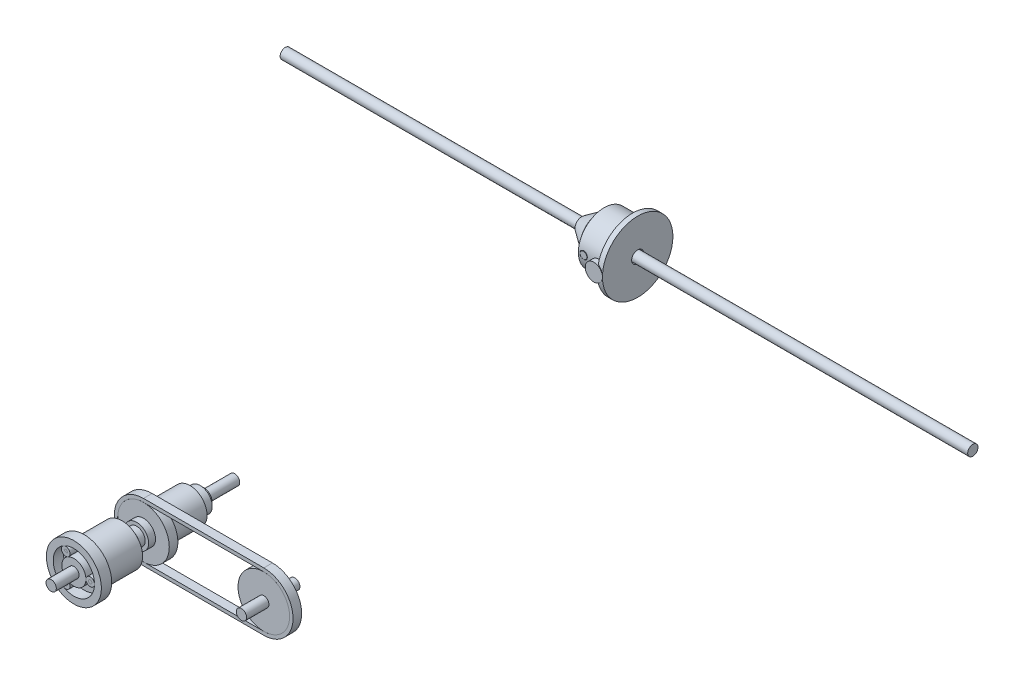
SolidWorks part; units mm, degrees
other "RD S Gear Inner"
other "RD S Gear Outer"
other "RD L Gear Left"
other "RD L Gear Right"
other "RD Ring Gear"
other "RD Pinion"
other "RD S Gear Inner"
ref_plane "Front Plane" through (0, 0, 0) normal (0, 0, 1) x (1, 0, 0)
ref_plane "Top Plane" through (0, 0, 0) normal (0, 1, 0) x (1, 0, 0)
ref_plane "Right Plane" through (0, 0, 0) normal (1, 0, 0) x (0, 0, -1)
sketch "Top View Layout" plane through (0, 0, 0) normal (0, 1, 0) x (1, 0, 0)
  line L0 (-100, 125) -> (100, 125)
  line L1 (0, 125) -> (0, -125)
  line L2 (-100, -125) -> (100, -125)
  line L3 (0, -15) -> (35, -15) construction
  line L4 (35, -15) -> (35, -125) construction
  line L5 (2.5, 114.75) -> (2.5, 135.25) construction
  line L6 (-2.5, 114.75) -> (2.5, 114.75) construction
  line L7 (-8.75, 127) -> (-2.75, 127) construction
  line L8 (-2.5, 114.75) -> (2.5, 114.75) construction
  line L9 (-2.5, 114.75) -> (-2.5, 116.25) construction
  line L10 (-2.5, 116.25) -> (2.5, 116.25) construction
  line L11 (2.5, 114.75) -> (2.5, 116.25) construction
  line L12 (2.5, 135.25) -> (1, 135.25) construction
  line L13 (2.5, 135.25) -> (2.5, 114.75) construction
  line L14 (2.5, 114.75) -> (1, 114.75) construction
  line L15 (1, 135.25) -> (1, 114.75) construction
  line L16 (-4.25, 128.5) -> (-2.75, 128.5) construction
  line L17 (-4.25, 128.5) -> (-4.25, 121.5) construction
  line L18 (-4.25, 121.5) -> (-2.75, 121.5) construction
  line L19 (-2.75, 128.5) -> (-2.75, 121.5) construction
  line L20 (-4.25, 128.5) -> (-2.75, 121.5) construction
  line L21 (-4.25, 121.5) -> (-2.75, 128.5) construction
  line L22 (-8.75, 128.5) -> (-7.25, 128.5) construction
  line L23 (-8.75, 128.5) -> (-8.75, 121.5) construction
  line L24 (-8.75, 121.5) -> (-7.25, 121.5) construction
  line L25 (-7.25, 128.5) -> (-7.25, 121.5) construction
  line L26 (-8.75, 128.5) -> (-7.25, 121.5) construction
  line L27 (-8.75, 121.5) -> (-7.25, 128.5) construction
  line L28 (-8.75, 123) -> (-2.75, 123) construction
  line L29 (-5.75, 123) -> (-5.75, 120.2863) construction
  line L30 (-5.75, 127) -> (-5.75, 129.2691) construction
  point P8 (0, 114.75)
  point P9 (0, 0)
  point P11 (2.5, 125)
  point P16 (2.5, 125)
  point P19 (0, 114.75)
  point P23 (-3.5, 125)
  point P28 (-8, 125)
  dimension "D1" = 250
  dimension "D2" = 200
  dimension "D3" = 35
  dimension "D4" = 15
  dimension "D5" = 5
  dimension "D6" = 20.5
  dimension "D7" = 1.5
  dimension "D8" = 1.5
  dimension "D9" = 1.5
  dimension "D10" = 7
  dimension "D11" = 3.5
  dimension "D12" = 8
  dimension "D13" = 1.5
  dimension "D14" = 1.5
ref_plane "Left" through (100, 0, 0) normal (-1, 0, 0) x (0, 0, 1)
ref_plane "Right" through (-100, 0, 0) normal (-1, 0, 0) x (0, 0, 1)
sketch "Left Wheels" plane through (100, 0, 0) normal (-1, 0, 0) x (0, 0, 1)
  circle A0 centre (125, 0) radius 25
  circle A1 centre (-125, 0) radius 25
  dimension "D1" = 50
  dimension "D2" = 50
sketch "Right Wheels" plane through (-100, 0, 0) normal (-1, 0, 0) x (0, 0, 1)
  circle A0 centre (-125, 0) radius 25 construction
  circle A1 centre (125, 0) radius 25 construction
  circle A2 centre (-125, 0) radius 25
  circle A3 centre (125, 0) radius 25
ref_plane "Rear Differential Pinion Plane" through (0, 0, -114.75) normal (0, 0, 1) x (1, 0, 0)
sketch "Rear Differential Pinion Profile" plane through (0, 0, -114.75) normal (0, 0, 1) x (1, 0, 0)
  circle A0 centre (0, 0) radius 2.5
ref_plane "Rear Differential Ring Gear Plane" through (2.5, 0, 0) normal (1, 0, 0) x (0, 0, -1)
ref_plane "Rear Axle" through (0, 0, -125) normal (0, 0, 1) x (1, 0, 0)
sketch "Rear Differential Ring Gear Profile" plane through (2.5, 0, 0) normal (1, 0, 0) x (0, 0, -1)
  line L0 (114.75, 0) -> (135.25, 0) construction
  circle A0 centre (125, 0) radius 10.25
extrude "Rear Differential Pinion" add sketch "Rear Differential Pinion Profile" against normal blind 1.5 contours A0
extrude "Rear Differential Ring Gear" add sketch "Rear Differential Ring Gear Profile" against normal blind 1.5 separate body contours A0
ref_plane "RD Inner L Gear Plane" through (-2.75, 0, 0) normal (1, 0, 0) x (0, 0, -1)
ref_plane "RD Outer L Gear Plane" through (-8.75, 0, 0) normal (1, 0, 0) x (0, 0, -1)
sketch "RD Inner L Gear Profile" plane through (-2.75, 0, 0) normal (1, 0, 0) x (0, 0, -1)
  circle A0 centre (125, 0) radius 3.5
sketch "RD Outer L Gear Profile" plane through (-8.75, 0, 0) normal (1, 0, 0) x (0, 0, -1)
  line L0 (128.5, 0) -> (121.5, 0) construction
  circle A0 centre (125, 0) radius 3.5
ref_plane "RD Inner S Gear Plane" through (0, 0, -121.5) normal (0, 0, 1) x (1, 0, 0)
ref_plane "RD Outer S Gear Plane" through (0, 0, -128.5) normal (0, 0, 1) x (1, 0, 0)
sketch "RD Inner S Gear Profile" plane through (0, 0, -121.5) normal (0, 0, 1) x (1, 0, 0)
  line L0 (-8.75, 0) -> (-7.25, 0) construction
  circle A0 centre (-5.75, 0) radius 3
sketch "RD Outer S Gear Profile" plane through (0, 0, -128.5) normal (0, 0, 1) x (1, 0, 0)
  line L0 (-8.75, 0) -> (-7.25, 0) construction
  circle A2 centre (-5.75, 0) radius 3
extrude "RD Outer L Gear Extrude" add sketch "RD Outer L Gear Profile" along normal blind 1.5 separate body contours A0
extrude "RD Inner L Gear Extrude" add sketch "RD Inner L Gear Profile" against normal blind 1.5 separate body contours A0
extrude "RD Outer S Gear Extrude" add sketch "RD Outer S Gear Profile" along normal blind 1.5 separate body contours A2
extrude "RD Inner S Gear Extrude" add sketch "RD Inner S Gear Profile" against normal blind 1.5 separate body contours A0
sketch "RD Ring Gear Case Profile" plane through (1, 0, 0) normal (-1, 0, 0) x (0, 0, 1)
  line L0 (-121.5, 3.2113) -> (-121.5, -3.2113)
  line L1 (-128.5, 3.2113) -> (-128.5, -3.2113)
  line L2 (-121.5, 6.6332) -> (-121.5, 3.2113) construction
  line L3 (-128.5, 6.6332) -> (-128.5, 3.2113) construction
  line L4 (-121.5, -3.2113) -> (-121.5, -6.6332) construction
  line L5 (-128.5, -3.2113) -> (-128.5, -6.6332) construction
  circle A0 centre (-125, 0) radius 7.5
  arc A1 (-121.5, 3.2113) -> (-128.5, 3.2113) centre (-125, 0) ccw
  arc A2 (-121.5, -3.2113) -> (-121.5, 3.2113) centre (-125, 0) ccw construction
  arc A3 (-128.5, 3.2113) -> (-128.5, -3.2113) centre (-125, 0) ccw construction
  arc A4 (-128.5, -3.2113) -> (-121.5, -3.2113) centre (-125, 0) ccw
  point P7 (-121.5, 0)
  dimension "D1" = 15
  dimension "D2" = 9.5
extrude "RD Ring Gear Case " add sketch "RD Ring Gear Case Profile" along normal blind 8.25
sketch "Sketch11" plane through (-7.25, 0, 0) normal (-1, 0, 0) x (0, 0, 1)
  circle A0 centre (-125, 0) radius 5.5
  circle A1 centre (-125, 0) radius 4.75
  arc A2 (-121.5, 3.2113) -> (-128.5, 3.2113) centre (-125, 0) ccw construction
  dimension "D1" = 11
extrude "Boss-Extrude8" add sketch "Sketch11" along normal up to vertex up to point (-8.75, 0, -128.5)
fillet "Fillet1" radius 2 1 edges at (-7.25, 0, -119.5)
sketch "Sketch12" plane through (0, 0, -125) normal (0, 0, 1) x (1, 0, 0)
  line L0 (-8.75, 0) -> (-13.75, 0) construction
  line L1 (-8.75, 0) -> (-7.25, 0) construction
  line L2 (-8.75, 0) -> (-7.25, 0) construction
  line L3 (-100, 0) -> (100, 0) construction
  line L4 (-100, 0) -> (100, 0) construction
  line L5 (-8.75, 5.5) -> (-8.75, -5.5) construction
  line L6 (-13.75, 0) -> (-13.75, 2)
  line L7 (-13.75, 2) -> (-8.75, 5.5)
  line L8 (-13.75, 0) -> (-8.75, 0)
  line L9 (-8.75, 0) -> (-8.75, 5.5)
  point P15 (-13.75, 1)
  dimension "D1" = 5
  dimension "D2" = 2
revolve "Revolve1" add sketch "Sketch12" angle 360 about L0
sketch "Sketch13" plane through (2.5, 0, 0) normal (1, 0, 0) x (0, 0, -1)
  circle A0 centre (125, 0) radius 1.75
  dimension "D1" = 3.5
extrude "Cut-Extrude1" cut sketch "Sketch13" against normal through all
sketch "Sketch14" plane through (0, 0, -121.5) normal (0, 0, 1) x (1, 0, 0)
  circle A0 centre (-5.75, 0) radius 1
  dimension "D1" = 2
extrude "Boss-Extrude9" add sketch "Sketch14" along normal blind 4
sketch "Sketch15" plane through (0, 0, -121.5) normal (0, 0, 1) x (1, 0, 0)
  circle A0 centre (-5.75, 0) radius 1.1
  dimension "D1" = 2.2
extrude "Cut-Extrude2" cut sketch "Sketch15" against normal through all both and the other way through all
extrude "Boss-Extrude10" add sketch "Sketch14<2>" against normal blind 4 from surface starting at face at (-2.75, 0, -128.5)
sketch "Sketch14<2>" plane through (0, 0, -121.5) normal (0, 0, 1) x (1, 0, 0) same geometry as "Sketch14"
sketch "Sketch16" plane through (-8.75, 0, 0) normal (-1, 0, 0) x (0, 0, 1)
  circle A0 centre (-125, 0) radius 1.5
  dimension "D1" = 3
extrude "Boss-Extrude11" add sketch "Sketch16" along normal up to vertex (91.25 mm away) up to point (-100, 0, -125)
sketch "Sketch17" plane through (-2.75, 0, 0) normal (1, 0, 0) x (0, 0, -1)
  circle A0 centre (125, 0) radius 1.5 construction
  circle A1 centre (125, 0) radius 1.5
extrude "Boss-Extrude12" add sketch "Sketch17" along normal up to vertex (102.75 mm away) up to point (100, 0, -125)
sketch "Transfer Case Layout" plane through (0, 0, 0) normal (0, 1, 0) x (1, 0, 0)
  line L0 (0, 125) -> (0, -125) construction
  line L1 (-7.5, -13.75) -> (7.5, -13.75)
  line L2 (-7.5, -13.75) -> (-7.5, -16.25)
  line L3 (-7.5, -16.25) -> (7.5, -16.25)
  line L4 (7.5, -13.75) -> (7.5, -16.25)
  line L5 (-7.5, -13.75) -> (7.5, -16.25) construction
  line L6 (-7.5, -16.25) -> (7.5, -13.75) construction
  line L7 (27.5, -13.75) -> (42.5, -13.75)
  line L8 (27.5, -13.75) -> (27.5, -16.25)
  line L9 (27.5, -16.25) -> (42.5, -16.25)
  line L10 (42.5, -13.75) -> (42.5, -16.25)
  line L11 (27.5, -13.75) -> (42.5, -16.25) construction
  line L12 (27.5, -16.25) -> (42.5, -13.75) construction
  line L13 (2.5, -17.25) -> (-2.5, -17.25)
  line L14 (2.5, -17.25) -> (2.5, -16.25)
  line L15 (2.5, -16.25) -> (-2.5, -16.25)
  line L16 (-2.5, -17.25) -> (-2.5, -16.25)
  line L17 (2.5, -17.25) -> (-2.5, -16.25) construction
  line L18 (2.5, -16.25) -> (-2.5, -17.25) construction
  line L19 (-2, -4.75) -> (-2, -10.75)
  line L20 (3.5, -18.25) -> (-3.5, -18.25)
  line L21 (3.5, -18.25) -> (3.5, -16.25)
  line L22 (3.5, -16.25) -> (-3.5, -16.25)
  line L23 (-3.5, -18.25) -> (-3.5, -16.25)
  line L24 (3.5, -18.25) -> (-3.5, -16.25) construction
  line L25 (3.5, -16.25) -> (-3.5, -18.25) construction
  line L26 (2.5, -20) -> (-2.5, -20)
  line L27 (2.5, -20) -> (2.5, -17.5)
  line L28 (2.5, -17.5) -> (-2.5, -17.5)
  line L29 (-2.5, -20) -> (-2.5, -17.5)
  line L30 (2.5, -20) -> (-2.5, -17.5) construction
  line L31 (2.5, -17.5) -> (-2.5, -20) construction
  line L32 (-3.5, -9.25) -> (3.5, -9.25)
  line L33 (-3.5, -9.25) -> (-3.5, -10.75)
  line L34 (-3.5, -10.75) -> (3.5, -10.75)
  line L35 (3.5, -9.25) -> (3.5, -10.75)
  line L36 (-3.5, -9.25) -> (3.5, -10.75) construction
  line L37 (-3.5, -10.75) -> (3.5, -9.25) construction
  line L38 (-3.5, -4.75) -> (3.5, -4.75)
  line L39 (-3.5, -4.75) -> (-3.5, -6.25)
  line L40 (-3.5, -6.25) -> (3.5, -6.25)
  line L41 (3.5, -4.75) -> (3.5, -6.25)
  line L42 (-3.5, -4.75) -> (3.5, -6.25) construction
  line L43 (-3.5, -6.25) -> (3.5, -4.75) construction
  line L44 (2, -4.75) -> (2, -10.75)
  line L45 (0, -6.25) -> (0, -9.25) construction
  line L46 (-5, -2.75) -> (5, -2.75) construction
  line L47 (-5, -2.75) -> (-5, -12.75) construction
  line L48 (-5, -12.75) -> (5, -12.75) construction
  line L49 (5, -2.75) -> (5, -12.75) construction
  line L50 (-5, -2.75) -> (5, -12.75) construction
  line L51 (-5, -12.75) -> (5, -2.75) construction
  line L52 (-6, -22.5) -> (-6, -24)
  line L53 (-2.5, -1.75) -> (2.5, -1.75)
  line L54 (-2.5, -1.75) -> (-2.5, -2.75)
  line L55 (-2.5, -2.75) -> (2.5, -2.75)
  line L56 (2.5, -1.75) -> (2.5, -2.75)
  line L57 (-2.5, -1.75) -> (2.5, -2.75) construction
  line L58 (-2.5, -2.75) -> (2.5, -1.75) construction
  line L59 (-2.5, 1.25) -> (2.5, 1.25)
  line L60 (-2.5, 1.25) -> (-2.5, -0.75)
  line L61 (-2.5, -0.75) -> (2.5, -0.75)
  line L62 (2.5, 1.25) -> (2.5, -0.75)
  line L63 (-2.5, 1.25) -> (2.5, -0.75) construction
  line L64 (-2.5, -0.75) -> (2.5, 1.25) construction
  line L65 (3.5, 0.25) -> (-3.5, 0.25)
  line L66 (3.5, 0.25) -> (3.5, -2.25)
  line L67 (3.5, -2.25) -> (-3.5, -2.25)
  line L68 (-3.5, 0.25) -> (-3.5, -2.25)
  line L69 (3.5, 0.25) -> (-3.5, -2.25) construction
  line L70 (3.5, -2.25) -> (-3.5, 0.25) construction
  line L71 (-2.5, -22.5) -> (2.5, -22.5)
  line L72 (-2.5, -22.5) -> (-2.5, -27.5)
  line L73 (-2.5, -27.5) -> (2.5, -27.5)
  line L74 (2.5, -22.5) -> (2.5, -27.5)
  line L75 (-2.5, -22.5) -> (2.5, -27.5) construction
  line L76 (-2.5, -27.5) -> (2.5, -22.5) construction
  line L77 (-6, -24) -> (6, -24)
  line L78 (6, -24) -> (6, -22.5)
  line L79 (6, -22.5) -> (-6, -22.5)
  line L80 (-4.5, -22.5) -> (-4.5, -24)
  line L81 (4.5, -22.5) -> (4.5, -24)
  line L82 (-6, -24) -> (-6, -33.5) construction
  line L83 (2.5, -29.5) -> (-2.5, -29.5)
  line L84 (2.5, -29.5) -> (2.5, -28)
  line L85 (2.5, -28) -> (-2.5, -28)
  line L86 (-2.5, -29.5) -> (-2.5, -28)
  line L87 (2.5, -29.5) -> (-2.5, -28) construction
  line L88 (2.5, -28) -> (-2.5, -29.5) construction
  line L89 (-4.5, -26.5) -> (4.5, -26.5)
  line L90 (-4.5, -26.5) -> (-4.5, -29.5)
  line L91 (-4.5, -29.5) -> (4.5, -29.5)
  line L92 (4.5, -26.5) -> (4.5, -29.5)
  line L93 (-4.5, -26.5) -> (4.5, -29.5) construction
  line L94 (-4.5, -29.5) -> (4.5, -26.5) construction
  line L95 (6, -24) -> (6, -33.5) construction
  line L96 (-3.5, -33.5) -> (-3.5, -36.5)
  line L97 (6, -36.5) -> (-6, -36.5)
  line L98 (6, -36.5) -> (6, -33.5)
  line L99 (6, -33.5) -> (-6, -33.5)
  line L100 (-6, -36.5) -> (-6, -33.5)
  line L101 (6, -36.5) -> (-6, -33.5) construction
  line L102 (6, -33.5) -> (-6, -36.5) construction
  line L103 (3.5, -33.5) -> (3.5, -36.5)
  line L104 (0, -28) -> (0, -43.1129)
  line L109 (8, -36.5) -> (-8, -36.5)
  line L110 (8, -36.5) -> (8, -33.5)
  line L111 (8, -33.5) -> (-8, -33.5)
  line L112 (-8, -36.5) -> (-8, -33.5)
  line L113 (8, -36.5) -> (-8, -33.5) construction
  line L114 (8, -33.5) -> (-8, -36.5) construction
  line L115 (0, -27.5) -> (0, -9.25)
  line L116 (0, -6.25) -> (0, -1.75)
  line L117 (0, -0.75) -> (0, 11.0375)
  line L118 (35, -22.7597) -> (35, -7.2403)
  point P0 (0, -15)
  point P6 (35, -15)
  point P12 (0, -16.75)
  point P19 (0, -17.25)
  point P24 (0, -18.75)
  point P29 (0, -10)
  point P34 (0, -5.5)
  point P43 (0, -7.75)
  point P50 (0, -2.25)
  point P55 (0, 0.25)
  point P60 (0, -1)
  point P65 (0, -25)
  point P72 (0, -22.5)
  point P79 (0, -28.75)
  point P84 (0, -28)
  point P92 (0, -35)
  point P98 (0, -35)
  point P99 (0, -35)
  point P110 (0, 0)
  point P113 (35, -15)
  point P114 (0, 0)
  point P115 (0, 0)
  point P116 (0, 0)
  point P117 (0, 0)
  point P118 (0, 0)
  point P119 (0, 0)
  point P120 (0, 0)
  point P121 (0, 0)
  point P122 (0, 0)
  point P123 (0, 0)
  point P124 (0, 0)
  point P125 (0, 0)
  point P126 (6, -33.5)
  point P127 (0, 0)
  point P128 (0, 0)
  point P129 (0, 0)
  point P130 (0, 0)
  point P131 (0, 0)
  point P132 (0, 0)
  point P133 (2.5, -1.75)
  point P134 (0, 0)
  point P135 (0, 0)
  point P136 (0, 0)
  point P137 (0, 0)
  point P138 (0, 0)
  point P139 (0, 0)
  point P140 (0, 0)
  point P141 (0, 0)
  point P142 (0, 0)
  point P143 (0, 0)
  point P144 (0, 0)
  point P145 (0, 0)
  point P146 (0, 0)
  point P147 (0, 0)
  point P148 (0, 0)
  point P149 (0, 0)
  dimension "D1" = 2.5
  dimension "D2" = 2.5
  dimension "D3" = 15
  dimension "D4" = 15
  dimension "D5" = 1
  dimension "D6" = 5
  dimension "D7" = 7
  dimension "D8" = 2
  dimension "D9" = 0.25
  dimension "D10" = 2.5
  dimension "D11" = 7
  dimension "D12" = 5
  dimension "D13" = 1.5
  dimension "D14" = 1.5
  dimension "D15" = 1.5
  dimension "D16" = 1.5
  dimension "D17" = 6
  dimension "D18" = 2
  dimension "D19" = 1.5
  dimension "D20" = 5
  dimension "D21" = 1
  dimension "D22" = 2
  dimension "D23" = 1
  dimension "D24" = 7
  dimension "D25" = 2.5
  dimension "D26" = 0.5
  dimension "D27" = 5
  dimension "D28" = 5
  dimension "D29" = 10
  dimension "D30" = 1.5
  dimension "D31" = 12
  dimension "D32" = 1.5
  dimension "D33" = 1.5
  dimension "D34" = 1.5
  dimension "D35" = 0.5
  dimension "D36" = 3
  dimension "D37" = 3
  dimension "D38" = 20
  dimension "D39" = 2.5
  dimension "D40" = 2.5
  dimension "D41" = 7
  dimension "D42" = 2
  dimension "D43" = 16
ref_plane "FWD Sprocket Plane" through (0, 0, 15) normal (0, 0, 1) x (1, 0, 0)
sketch "Sketch19" plane through (0, 0, 15) normal (0, 0, 1) x (1, 0, 0)
  circle A0 centre (35, 0) radius 7.5
  circle A1 centre (0, 0) radius 7.5
  point P6 (7.5, 0)
  point P9 (27.5, 0)
extrude "FWD Sprockets" add sketch "Sketch19" along normal up to vertex (1.25 mm away) and the other way up to vertex (1.25 mm away) separate body up to point (-7.5, 0, 16.25) other way up to point (-7.5, 0, 13.75)
sketch "Sketch20" plane through (0, 0, 15) normal (0, 0, 1) x (1, 0, 0)
  line L0 (0, 8.5) -> (35, 8.5)
  line L1 (0, -8.5) -> (35, -8.5)
  line L2 (0, 7.5) -> (35, 7.5)
  line L3 (0, -7.5) -> (35, -7.5)
  circle A0 centre (0, 0) radius 7.5 construction
  arc A1 (0, 7.5) -> (0, -7.5) centre (0, 0) ccw
  circle A2 centre (35, 0) radius 7.5 construction
  arc A3 (35, -7.5) -> (35, 7.5) centre (35, 0) ccw
  arc A4 (0, 8.5) -> (0, -8.5) centre (0, 0) ccw
  arc A5 (35, -8.5) -> (35, 8.5) centre (35, 0) ccw
  arc A6 (4, -7.5) -> (4, 7.5) centre (0, 0) ccw construction
  arc A7 (0, -7.5) -> (0, 7.5) centre (0, 0) ccw construction
  arc A8 (35, 7.5) -> (35, -7.5) centre (35, 0) ccw construction
  arc A9 (31, 7.5) -> (31, -7.5) centre (35, 0) ccw construction
  arc A10 (4, 7.5) -> (0, 8.5) centre (0, 0) ccw construction
  arc A11 (35, 8.5) -> (31, 7.5) centre (35, 0) ccw construction
  arc A12 (31, -7.5) -> (35, -8.5) centre (35, 0) ccw construction
  arc A13 (0, -8.5) -> (4, -7.5) centre (0, 0) ccw construction
  dimension "D1" = 1
  dimension "D2" = 1
extrude "FWD Sprocket Chain" add sketch "Sketch20" along normal up to surface and the other way up to surface separate body up to face at (7.5, 0, 16.25) other way up to face at (7.5, 0, 13.75)
sketch "Sketch21" plane through (0, 0, 16.25) normal (0, 0, 1) x (1, 0, 0)
  circle A0 centre (0, 0) radius 2.5
  point P3 (2.5, 0)
extrude "FWD Sprocket Dog Gear" add sketch "Sketch21" along normal up to vertex (1 mm away) up to point (-2.5, 0, 17.25)
ref_plane "Mode Sleeve Gear Plane" through (0, 0, 18.25) normal (0, 0, 1) x (1, 0, 0)
sketch "Sketch22" plane through (0, 0, 18.25) normal (0, 0, 1) x (1, 0, 0)
  circle A0 centre (0, 0) radius 3.5
  circle A1 centre (0, 0) radius 2.5 construction
  circle A2 centre (0, 0) radius 2.5
extrude "Mode Sleeve Gear" add sketch "Sketch22" against normal up to vertex (2 mm away) separate body up to point (3.5, 0, 16.25)
sketch "Sketch23" plane through (0, 0, 18.25) normal (0, 0, 1) x (1, 0, 0)
  circle A0 centre (0, 0) radius 2.5 construction
  circle A1 centre (0, 0) radius 2.5
extrude "Mode Sleeve Main Shaft Gear" add sketch "Sketch23" along normal up to vertex (1.75 mm away) separate body up to point (2.5, 0, 20)
ref_plane "Range Sleeve Rear Plane" through (0, 0, 22.5) normal (0, 0, 1) x (1, 0, 0)
sketch "Sketch24" plane through (0, 0, 22.5) normal (0, 0, 1) x (1, 0, 0)
  circle A0 centre (0, 0) radius 2.5
extrude "Main Shaft Range Sleeve Gear" add sketch "Sketch24" along normal up to vertex (5 mm away) separate body up to point (-2.5, 0, 27.5)
sketch "Sketch25" plane through (0, 0, 22.5) normal (0, 0, 1) x (1, 0, 0)
  circle A0 centre (0, 0) radius 6
  circle A3 centre (0, 0) radius 4.5
extrude "Carrier Range Sleeve Gear" add sketch "Sketch25" along normal up to vertex (1.5 mm away) separate body up to point (6, 0, 24)
ref_plane "Range Sleeve Input Shaft Side" through (0, 0, 29.5) normal (0, 0, 1) x (1, 0, 0)
sketch "Sketch27" plane through (0, 0, 29.5) normal (0, 0, 1) x (1, 0, 0)
  circle A0 centre (0, 0) radius 2.5
extrude "Input Range Sleeve Gear" add sketch "Sketch27" against normal up to vertex (1.5 mm away) separate body up to point (2.5, 0, 28)
sketch "Sketch28" plane through (0, 0, 29.5) normal (0, 0, 1) x (1, 0, 0)
  circle A0 centre (0, 0) radius 4.5
  circle A1 centre (0, 0) radius 2.5 construction
  circle A2 centre (0, 0) radius 2.5
extrude "Range Sleeve Sleeve Gear" add sketch "Sketch28" against normal up to vertex (3 mm away) separate body up to point (4.5, 0, 26.5)
ref_plane "Planetary Input Side Plane" through (0, 0, 36.5) normal (0, 0, 1) x (1, 0, 0)
sketch "Sketch29" plane through (0, 0, 36.5) normal (0, 0, 1) x (1, 0, 0)
  circle A0 centre (0, 0) radius 3.5
extrude "Planetary Sun Gear" add sketch "Sketch29" against normal up to vertex (3 mm away) separate body up to point (3.5, 0, 33.5)
sketch "Sketch30" plane through (0, 0, 36.5) normal (0, 0, 1) x (1, 0, 0)
  line L0 (6, 0) -> (-6, 0) construction
  circle A0 centre (4.75, 0) radius 1.25
  point P3 (0, 0)
extrude "Planetary Planet Gear" add sketch "Sketch30" against normal up to vertex (3 mm away) separate body up to point (6, 0, 33.5)
pattern_circular "Planetary Planet Gear x 3" count 3 over 360 about axis through (0, 0, 28) along (0, 0, 1) reverse direction yes of bodies 132
sketch "Sketch31" plane through (0, 0, 36.5) normal (0, 0, 1) x (1, 0, 0)
  circle A0 centre (0, 0) radius 6
  circle A1 centre (0, 0) radius 8
extrude "Planetary Ring Gear" add sketch "Sketch31" against normal up to vertex (3 mm away) separate body up to point (8, 0, 33.5)
ref_plane "Planetary Rear Side Plane" through (0, 0, 33.5) normal (0, 0, 1) x (1, 0, 0)
sketch "Sketch32" plane through (0, 0, 33.5) normal (0, 0, 1) x (1, 0, 0)
  line L0 (3.5, 0) -> (6, 0) construction
  line L1 (0, 0) -> (4.75, 0) construction
  line L2 (0, 0) -> (-2.375, -4.1136) construction
  circle A0 centre (0, 0) radius 6
  circle A1 centre (4.75, 0) radius 0.5
  circle A2 centre (-2.375, -4.1136) radius 0.5
  circle A3 centre (-2.375, 4.1136) radius 0.5
  point P4 (4.75, 0)
  dimension "D1" = 1
  dimension "D3" = 120
  dimension "D4" = 4.75
  dimension "D2" = 3
extrude "Carrier" add sketch "Sketch32" against normal blind 1 separate body contours A3 | A0 A3 A2 A1 | A1 | A2 region at (0, 0, 33.5) region at (4.75, 0, 33.5) region at (-2.375, -4.1136, 33.5) region at (-2.375, 4.1136, 33.5)
extrude "Carrier Shafts" add sketch "Sketch32<3>" along normal up to vertex (3 mm away) contours A1 | A2 | A3 region at (4.75, 0, 33.5) region at (-2.375, -4.1136, 33.5) up to point (-3.5, 0, 36.5)
sketch "Sketch32<3>" plane through (0, 0, 33.5) normal (0, 0, 1) x (1, 0, 0) same geometry as "Sketch32"
sketch "Sketch33" plane through (0, 0, 33.5) normal (0, 0, 1) x (1, 0, 0)
  circle A0 centre (0, 0) radius 6 construction
  circle A1 centre (0, 0) radius 6
  circle A2 centre (0, 0) radius 5.5
  dimension "D1" = 0.5
extrude "Carrier Range Sleeve Gear Connect" add sketch "Sketch33" against normal up to surface (9.5 mm away) up to face at (6, 0, 24)
ref_plane "Center Diff Main Shaft Sidegear Plane" through (0, 0, 10.75) normal (0, 0, 1) x (1, 0, 0)
sketch "Sketch34" plane through (0, 0, 10.75) normal (0, 0, 1) x (1, 0, 0)
  circle A0 centre (0, 0) radius 3.5
extrude "Center Diff Main Shaft Side Gear" add sketch "Sketch34" against normal up to vertex (1.5 mm away) separate body up to point (3.5, 0, 9.25)
ref_plane "Center Diff Rear Shaft Sidegear Plane" through (0, 0, 4.75) normal (0, 0, 1) x (1, 0, 0)
ref_plane "Center Diff Mid Plane" through (0, 0, 7.75) normal (0, 0, 1) x (1, 0, 0)
mirror "Center Diff Rear Shaft Side Gear" about plane through (0, 0, 7.75) normal (0, 0, 1) of bodies 139
ref_plane "Center Diff Right Pinion Inner Plane" through (-2, 0, 0) normal (-1, 0, 0) x (0, 0, 1)
sketch "Sketch35" plane through (-2, 0, 0) normal (-1, 0, 0) x (0, 0, 1)
  line L0 (4.75, 0) -> (10.75, 0) construction
  circle A0 centre (7.75, 0) radius 3
extrude "Center Diff Right Pinion" add sketch "Sketch35" along normal up to vertex (1.5 mm away) separate body up to point (-3.5, 0, 10.75)
ref_plane "Center Diff Left Side Pinion Inner Plane" through (2, 0, 0) normal (-1, 0, 0) x (0, 0, 1)
sketch "Sketch36" plane through (2, 0, 0) normal (-1, 0, 0) x (0, 0, 1)
  line L0 (4.75, 0) -> (10.75, 0) construction
  circle A0 centre (7.75, 0) radius 3
extrude "Center Diff Left Pinion" add sketch "Sketch36" against normal up to vertex (1.5 mm away) separate body up to point (3.5, 0, 4.75)
ref_plane "Center Diff Rear Shaft Side Plane" through (0, 0, 2.75) normal (0, 0, 1) x (1, 0, 0)
sketch "Sketch37" plane through (0, 0, 2.75) normal (0, 0, 1) x (1, 0, 0)
  circle A0 centre (0, 0) radius 5
extrude "Center Diff Rear Axle Side Plate" add sketch "Sketch37" along normal up to vertex (2 mm away) separate body up to point (3.5, 0, 4.75)
mirror "Center Diff Main Shaft Side Plate" about plane through (0, 0, 7.75) normal (0, 0, 1) of bodies 143
sketch "Sketch38" plane through (0, 0, 2.75) normal (0, 0, 1) x (1, 0, 0)
  line L0 (3.5, -2.8284) -> (3.5, 2.8284)
  line L1 (-3.4263, -2.9173) -> (-3.5, -2.8284)
  line L2 (-3.5, -2.8284) -> (-3.5, 2.8284)
  circle A0 centre (0, 0) radius 5 construction
  circle A1 centre (0, 0) radius 5
  arc A2 (3.5, 2.8284) -> (-3.5, 2.8284) centre (0, 0) ccw
  arc A3 (3.5, -2.8284) -> (3.5, 2.8284) centre (0, 0) ccw construction
  arc A4 (-3.5, 2.8284) -> (-3.5, -2.8284) centre (0, 0) ccw construction
  arc A5 (-3.5, -2.8284) -> (3.5, -2.8284) centre (0, 0) ccw
  dimension "D1" = 0.5
extrude "Center Diff Case" add sketch "Sketch38" along normal up to surface (8 mm away) contours A1 A5 L2 A2 L0 region at (-4.8586, 0, 2.75) up to face at (5, 0, 10.75)
sketch "Sketch39" plane through (0, 0, 2.75) normal (0, 0, 1) x (1, 0, 0)
  circle A0 centre (0, 0) radius 2.5
extrude "Center Diff Lock Gear" add sketch "Sketch39" against normal up to vertex (1 mm away) up to point (2.5, 0, 1.75)
ref_plane "Lock Sleeve Plane" through (0, 0, -0.25) normal (0, 0, 1) x (1, 0, 0)
sketch "Sketch41" plane through (0, 0, -0.25) normal (0, 0, 1) x (1, 0, 0)
  circle A0 centre (0, 0) radius 3.5
  circle A1 centre (0, 0) radius 2.5 construction
  circle A2 centre (0, 0) radius 2.5
extrude "Lock Sleeve" add sketch "Sketch41" along normal up to vertex (2.5 mm away) separate body up to point (-3.5, 0, 2.25)
sketch "Sketch42" plane through (0, 0, -0.25) normal (0, 0, 1) x (1, 0, 0)
  circle A0 centre (0, 0) radius 2.5 construction
  circle A1 centre (0, 0) radius 2.5
extrude "Lock Sleeve Rear Shaft Gear" add sketch "Sketch42" along normal up to vertex (1 mm away) and the other way up to vertex (1 mm away) separate body up to point (2.5, 0, 0.75) other way up to point (2.5, 0, -1.25)
sketch "Sketch43" plane through (-2, 0, 0) normal (-1, 0, 0) x (0, 0, 1)
  line L0 (4.75, 0) -> (10.75, 0) construction
  circle A0 centre (7.75, 0) radius 0.5
  dimension "D1" = 1
extrude "Center Diff Pinion Rotation Point Cut" cut sketch "Sketch43" against normal through all both and the other way through all
sketch "Sketch45" plane through (0, 0, 2.75) normal (0, 0, 1) x (1, 0, 0)
  circle A0 centre (0, 0) radius 0.5
  dimension "D1" = 1
extrude "Center Diff Side Gear Rotation Point" cut sketch "Sketch45" against normal through all both and the other way through all
sketch "Sketch46" plane through (0, 0, -0.25) normal (0, 0, 1) x (1, 0, 0)
  circle A0 centre (0, 0) radius 1.5
  dimension "D1" = 3
extrude "Rear Shaft" add sketch "Sketch46" along normal up to vertex (1 mm away) and the other way blind 10 up to point (0, 0, 0.75)
sketch "Sketch47" plane through (0, 0, 2.75) normal (0, 0, 1) x (1, 0, 0)
  circle A0 centre (0, 0) radius 0.5
  dimension "D1" = 1
extrude "Center Diff Rear Shaft Side Axle" add sketch "Sketch47" along normal up to vertex (3.5 mm away) and the other way up to vertex (1 mm away) up to point (0, 0, 6.25) other way up to point (0, 0, 1.75)
sketch "Sketch48" plane through (-2, 0, 0) normal (-1, 0, 0) x (0, 0, 1)
  circle A0 centre (7.75, 0) radius 0.5 construction
  circle A1 centre (7.75, 0) radius 0.5
extrude "Center Diff Right Side Pinion Axle" add sketch "Sketch48" along normal up to vertex (3 mm away) up to point (-5, 0, 12.75)
sketch "Sketch49" plane through (2, 0, 0) normal (-1, 0, 0) x (0, 0, 1)
  circle A0 centre (7.75, 0) radius 0.5 construction
  circle A1 centre (7.75, 0) radius 0.5
extrude "Center Diff Left Side Pinion Axle" add sketch "Sketch49" against normal up to vertex (3 mm away) up to point (5, 0, 2.75)
sketch "Sketch50" plane through (0, 0, 18.25) normal (0, 0, 1) x (1, 0, 0)
  circle A0 centre (0, 0) radius 0.5
  dimension "D1" = 1
extrude "Main Shaft Sprocket Rotation Point Cut" cut sketch "Sketch50" against normal through all both and the other way through all
extrude "Main Shaft Extrude" add sketch "Sketch50<2>" against normal up to vertex (9 mm away) and the other way up to vertex (9.25 mm away) up to point (0, 0, 9.25) other way up to point (0, 0, 27.5)
sketch "Sketch50<2>" plane through (0, 0, 18.25) normal (0, 0, 1) x (1, 0, 0) same geometry as "Sketch50"
sketch "Sketch52" plane through (0, 0, 36.5) normal (0, 0, 1) x (1, 0, 0)
  circle A0 centre (0, 0) radius 1.5
  dimension "D1" = 3
extrude "Input Shaft Carrier Cut" cut sketch "Sketch52" against normal through all both and the other way through all
extrude "Input Shaft" add sketch "Sketch52<2>" along normal up to vertex (6.6129 mm away) and the other way up to vertex (8.5 mm away) up to point (0, 0, 43.1129) other way up to point (0, 0, 28)
sketch "Sketch52<2>" plane through (0, 0, 36.5) normal (0, 0, 1) x (1, 0, 0) same geometry as "Sketch52"
sketch "Sketch54" plane through (0, 0, 15) normal (0, 0, 1) x (1, 0, 0)
  circle A0 centre (35, 0) radius 1.5
  dimension "D1" = 3
extrude "FW Shaft" add sketch "Sketch54" along normal up to vertex (7.7597 mm away) and the other way up to vertex (7.7597 mm away) up to point (35, 0, 22.7597) other way up to point (35, 0, 7.2403)
